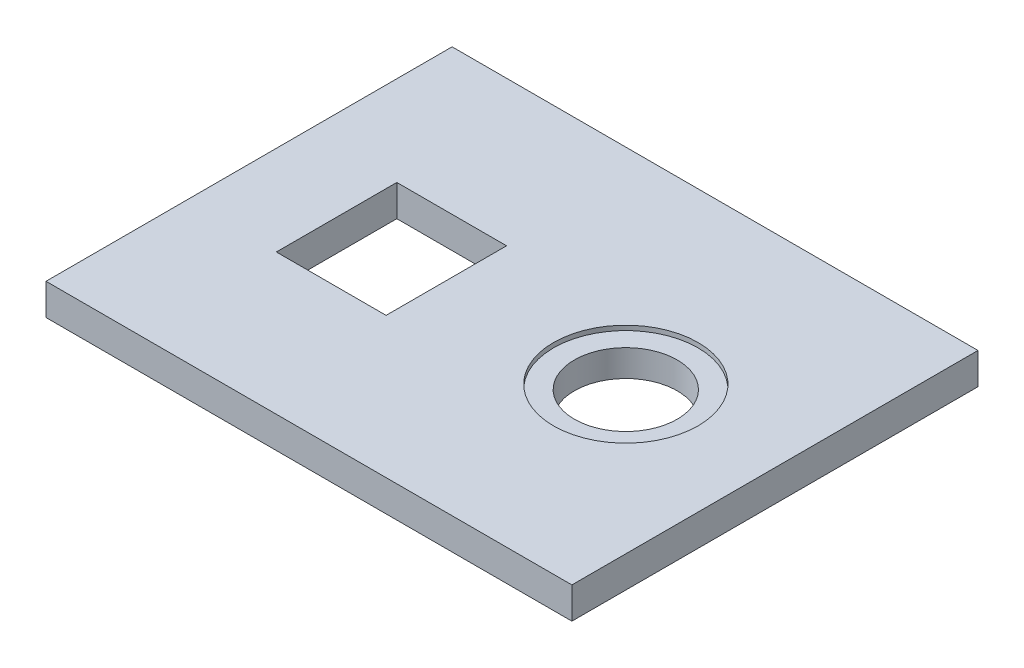
SolidWorks part; units mm, degrees
ref_plane "Front Plane" through (0, 0, 0) normal (0, 0, 1) x (1, 0, 0)
ref_plane "Top Plane" through (0, 0, 0) normal (0, 1, 0) x (1, 0, 0)
ref_plane "Right Plane" through (0, 0, 0) normal (1, 0, 0) x (0, 0, -1)
sketch "Sketch2" plane through (0, 0, 0) normal (0, 1, 0) x (1, 0, 0)
  line L1 (96.45, 76.7) -> (-100, 76.7)
  line L2 (96.45, 76.7) -> (96.45, -75)
  line L3 (96.45, -75) -> (-100, -75)
  line L4 (-100, 76.7) -> (-100, -75)
  line L5 (96.45, 76.7) -> (-100, -75) construction
  line L6 (96.45, -75) -> (-100, 76.7) construction
  point P0 (-1.775, 0.85)
  dimension "D1" = 151.7
  dimension "D2" = 196.45
extrude "Boss-Extrude1" add sketch "Sketch2" along normal blind 11.74 contours L4 L3 L2 L1
sketch "Sketch3" plane through (0, 0, 0) normal (0, 1, 0) x (1, 0, 0)
  line L0 (0, 0) -> (22.385, 0) construction
  line L1 (0, 0) -> (-25.4527, 0) construction
  line L6 (-66.4527, -22.5) -> (-25.4527, -22.5)
  line L7 (-66.4527, -22.5) -> (-66.4527, 22.5)
  line L8 (-25.4527, -22.5) -> (-25.4527, 22.5)
  line L9 (-66.4527, 22.5) -> (-25.4527, 22.5)
  line L10 (-66.4527, -22.5) -> (-25.4527, 22.5) construction
  line L11 (-25.4527, -22.5) -> (-66.4527, 22.5) construction
  circle A1 centre (41.585, 0) radius 19.2
  point P7 (-45.9527, 0)
  dimension "D1" = 38.4
  dimension "D2" = 41
  dimension "D4" = 25.4527
  dimension "D3" = 45
  dimension "D5" = 22.385
extrude "Cut-Extrude2" cut sketch "Sketch3" against normal blind 22 and the other way blind 15
sketch "Sketch4" plane through (0, 11.74, 0) normal (0, 1, 0) x (1, 0, 0)
  circle A0 centre (41.585, 0) radius 26.99
  dimension "D1" = 53.98
extrude "Cut-Extrude3" cut sketch "Sketch4" against normal blind 1.74
